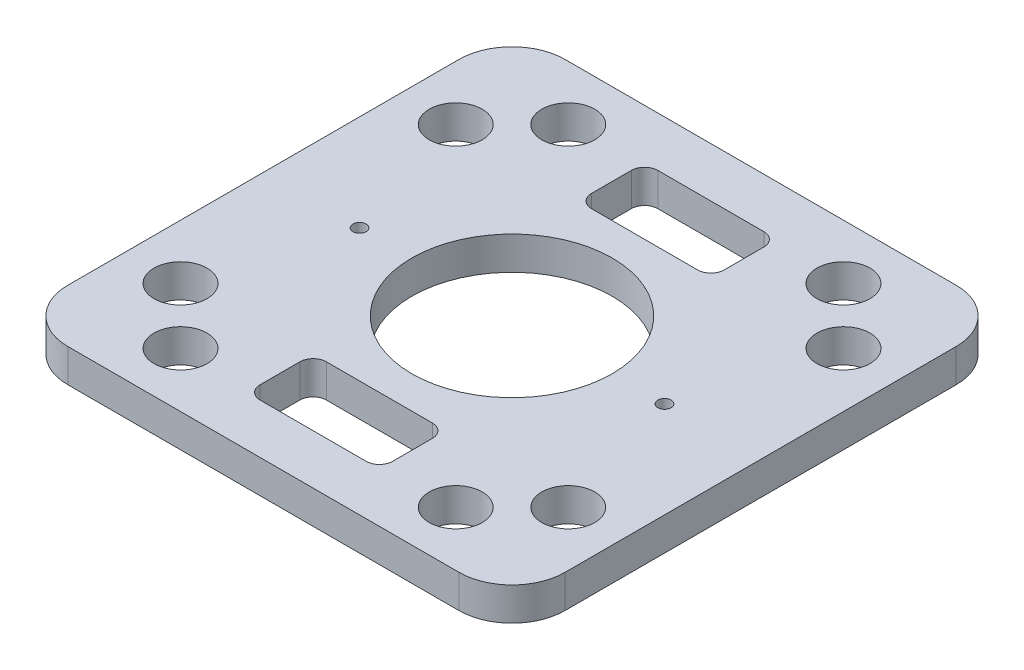
SolidWorks part; units mm, degrees
material "Balsa"
ref_plane "Front Plane" through (0, 0, 0) normal (0, 0, 1) x (1, 0, 0)
ref_plane "Top Plane" through (0, 0, 0) normal (0, 1, 0) x (1, 0, 0)
ref_plane "Right Plane" through (0, 0, 0) normal (1, 0, 0) x (0, 0, -1)
sketch "Sketch2" plane through (0, 0, 0) normal (0, 1, 0) x (1, 0, 0)
  line L0 (0, 0) -> (37.5, 0) construction
  line L1 (-37.5, -37.5) -> (37.5, -37.5)
  line L2 (-37.5, -37.5) -> (-37.5, 37.5)
  line L3 (-37.5, 37.5) -> (37.5, 37.5)
  line L4 (37.5, -37.5) -> (37.5, 37.5)
  line L5 (-37.5, -37.5) -> (37.5, 37.5) construction
  line L6 (-37.5, 37.5) -> (37.5, -37.5) construction
  line L7 (-25, -25) -> (25, -25) construction
  line L8 (-25, -25) -> (-25, 25) construction
  line L9 (-25, 25) -> (25, 25) construction
  line L10 (25, -25) -> (25, 25) construction
  line L11 (-25, -25) -> (25, 25) construction
  line L12 (-25, 25) -> (25, -25) construction
  line L13 (0, 0) -> (0, 37.5) construction
  line L14 (0, 0) -> (-23, 0) construction
  line L20 (-10, -20) -> (10, -20)
  line L21 (-10, 30) -> (10, 30)
  line L25 (20.7574, 29.2426) -> (29.2426, 20.7574) construction
  line L26 (-10, 30) -> (-10, 20)
  line L27 (-10, 20) -> (10, 20)
  line L28 (10, 30) -> (10, 20)
  line L29 (-10, 30) -> (10, 20) construction
  line L30 (-10, 20) -> (10, 30) construction
  line L31 (10, -30) -> (10, -20)
  line L32 (-10, -30) -> (10, -30)
  line L33 (-10, -30) -> (-10, -20)
  circle A0 centre (0, 0) radius 15.1197
  circle A5 centre (-23, 0) radius 1
  circle A6 centre (23, 0) radius 1
  circle A7 centre (29.2426, 20.7574) radius 4
  circle A8 centre (20.7574, 29.2426) radius 4
  circle A9 centre (-20.7574, -29.2426) radius 4
  circle A10 centre (-29.2426, -20.7574) radius 4
  circle A11 centre (-20.7574, 29.2426) radius 4
  circle A12 centre (-29.2426, 20.7574) radius 4
  circle A13 centre (29.2426, -20.7574) radius 4
  circle A14 centre (20.7574, -29.2426) radius 4
  point P0 (0, 0)
  point P6 (0, 0)
  point P18 (25, 25)
  point P23 (0, 25)
  dimension "D1" = 75
  dimension "D2" = 50
extrude "Boss-Extrude2" add sketch "Sketch2" along normal blind 5
fillet "Fillet1" radius 8 4 edges at (-37.5, 2.5, 37.5) (-37.5, 2.5, -37.5) (37.5, 2.5, 37.5) (37.5, 2.5, -37.5)
fillet "Fillet2" radius 2 8 edges at (-10, 2.5, 20) (-10, 2.5, 30) (10, 2.5, 30) (10, 2.5, 20) (-10, 2.5, -20) (-10, 2.5, -30) (10, 2.5, -20) (10, 2.5, -30)
